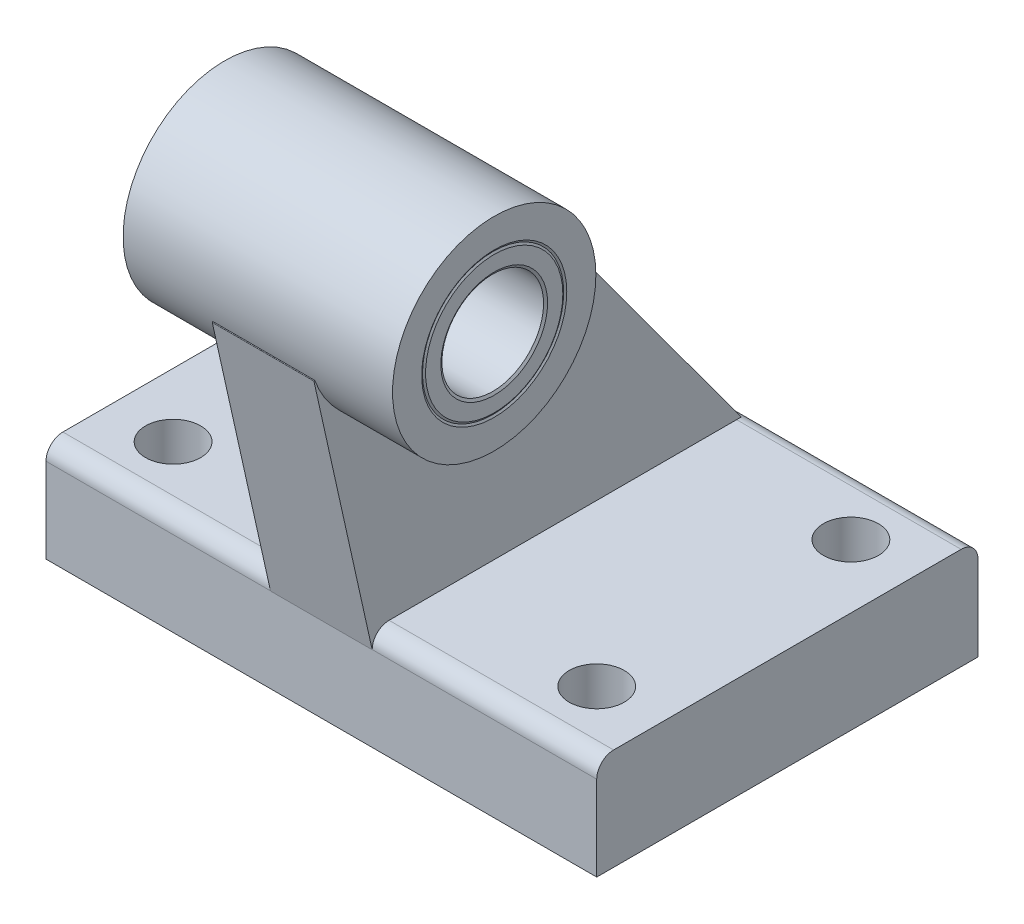
SolidWorks part; units mm, degrees
ref_plane "Front Plane" through (0, 0, 0) normal (0, 0, 1) x (1, 0, 0)
ref_plane "Top Plane" through (0, 0, 0) normal (0, 1, 0) x (1, 0, 0)
ref_plane "Right Plane" through (0, 0, 0) normal (1, 0, 0) x (0, 0, -1)
ref_plane "Plane1" through (0, 0, 0) normal (1, 0, 0) x (0, 0, -1)
sketch "Sketch1" plane through (0, 0, 0) normal (1, 0, 0) x (0, 0, -1)
  line L0 (-22.5, 10.008) -> (-22.5, 0)
  line L1 (-22.5, 0) -> (22.5, 0)
  line L2 (22.5, 0) -> (22.5, 10.008)
  line L3 (20.508, 12) -> (-20.508, 12)
  arc A0 (22.5, 10.008) -> (20.508, 12) centre (20.508, 10.008) ccw
  arc A1 (-20.508, 12) -> (-22.5, 10.008) centre (-20.508, 10.008) ccw
extrude "Boss-Extrude1" add sketch "Sketch1" against normal blind 32.5 and the other way blind 32.5
ref_plane "Plane2" through (0, 0, 0) normal (1, 0, 0) x (0, 0, -1)
sketch "Sketch2" plane through (0, 0, 0) normal (1, 0, 0) x (0, 0, -1)
  line L0 (-29.3768, 40.8807) -> (-22.5, 9.984)
  line L1 (-20.484, 12) -> (21.0412, 12)
  line L2 (21.0412, 12) -> (-7.4032, 50.8403)
  arc A0 (-29.281, 40.9086) -> (-29.3768, 40.8807) centre (-29.328, 40.8916) ccw
  arc A1 (-22.5, 9.984) -> (-20.484, 12) centre (-20.484, 9.984) cw
  arc A2 (-7.4032, 50.8403) -> (-7.4874, 50.7866) centre (-7.4436, 50.8107) ccw
  arc A3 (-7.4874, 50.7866) -> (-29.281, 40.9086) centre (-18, 45) cw
extrude "Boss-Extrude2" add sketch "Sketch2" against normal blind 6 and the other way blind 6
ref_plane "Plane3" through (0, 0, 0) normal (1, 0, 0) x (0, 0, -1)
sketch "Sketch3" plane through (0, 0, 0) normal (1, 0, 0) x (0, 0, -1)
  circle A0 centre (-18, 45) radius 12
extrude "Boss-Extrude3" add sketch "Sketch3" against normal blind 15.9 and the other way blind 15.9
ref_plane "Plane4" through (0, 0, 15) normal (0, 0, 1) x (1, 0, 0)
sketch "Sketch4" plane through (0, 0, 15) normal (0, 0, 1) x (1, 0, 0)
  line L0 (-25, 0) -> (-28.25, 0)
  line L1 (-28.25, 0) -> (-28.25, 12)
  line L2 (-28.25, 12) -> (-25, 12)
  line L3 (-25, 12) -> (-25, 0)
  line L4 (-25, 12) -> (-25, 0) construction
revolve "Cut-Revolve1" cut sketch "Sketch4" angle 360 about L4
ref_plane "Plane5" through (0, 0, 15) normal (0, 0, 1) x (1, 0, 0)
sketch "Sketch5" plane through (0, 0, 15) normal (0, 0, 1) x (1, 0, 0)
  line L0 (25, 0) -> (21.75, 0)
  line L1 (21.75, 0) -> (21.75, 12)
  line L2 (21.75, 12) -> (25, 12)
  line L3 (25, 12) -> (25, 0)
  line L4 (25, 12) -> (25, 0) construction
revolve "Cut-Revolve2" cut sketch "Sketch5" angle 360 about L4
ref_plane "Plane6" through (0, 0, -15) normal (0, 0, 1) x (1, 0, 0)
sketch "Sketch6" plane through (0, 0, -15) normal (0, 0, 1) x (1, 0, 0)
  line L0 (-25, 0) -> (-28.25, 0)
  line L1 (-28.25, 0) -> (-28.25, 12)
  line L2 (-28.25, 12) -> (-25, 12)
  line L3 (-25, 12) -> (-25, 0)
  line L4 (-25, 12) -> (-25, 0) construction
revolve "Cut-Revolve3" cut sketch "Sketch6" angle 360 about L4
ref_plane "Plane7" through (0, 0, -15) normal (0, 0, 1) x (1, 0, 0)
sketch "Sketch7" plane through (0, 0, -15) normal (0, 0, 1) x (1, 0, 0)
  line L0 (25, 0) -> (21.75, 0)
  line L1 (21.75, 0) -> (21.75, 12)
  line L2 (21.75, 12) -> (25, 12)
  line L3 (25, 12) -> (25, 0)
  line L4 (25, 12) -> (25, 0) construction
revolve "Cut-Revolve4" cut sketch "Sketch7" angle 360 about L4
ref_plane "Plane8" through (0, 0, 18) normal (0, 0, 1) x (1, 0, 0)
sketch "Sketch8" plane through (0, 0, 18) normal (0, 0, 1) x (1, 0, 0)
  line L0 (-15.9, 45) -> (-15.9, 53.564)
  line L1 (-15.9, 53.564) -> (-15.6113, 53.064)
  line L2 (-15.6113, 53.064) -> (15.6113, 53.064)
  line L3 (15.6113, 53.064) -> (15.9, 53.564)
  line L4 (15.9, 53.564) -> (15.9, 45)
  line L5 (15.9, 45) -> (-15.9, 45)
  line L6 (15.9, 45) -> (-15.9, 45) construction
revolve "Cut-Revolve5" cut sketch "Sketch8" angle 360 about L6
ref_plane "Plane9" through (0, 0, 18) normal (0, 0, 1) x (1, 0, 0)
sketch "Sketch9" plane through (0, 0, 18) normal (0, 0, 1) x (1, 0, 0)
  line L0 (-15.9, 51.3) -> (-15.7268, 51)
  line L1 (-15.7268, 51) -> (15.7268, 51)
  line L2 (15.7268, 51) -> (15.9, 51.3)
  line L3 (15.9, 51.3) -> (15.9, 53.1)
  line L4 (15.9, 53.1) -> (15.7268, 53.4)
  line L5 (15.7268, 53.4) -> (-15.7268, 53.4)
  line L6 (-15.7268, 53.4) -> (-15.9, 53.1)
  line L7 (-15.9, 53.1) -> (-15.9, 51.3)
  line L8 (15.9, 45) -> (-15.9, 45) construction
revolve "Revolve1" add sketch "Sketch9" angle 360 about L8
